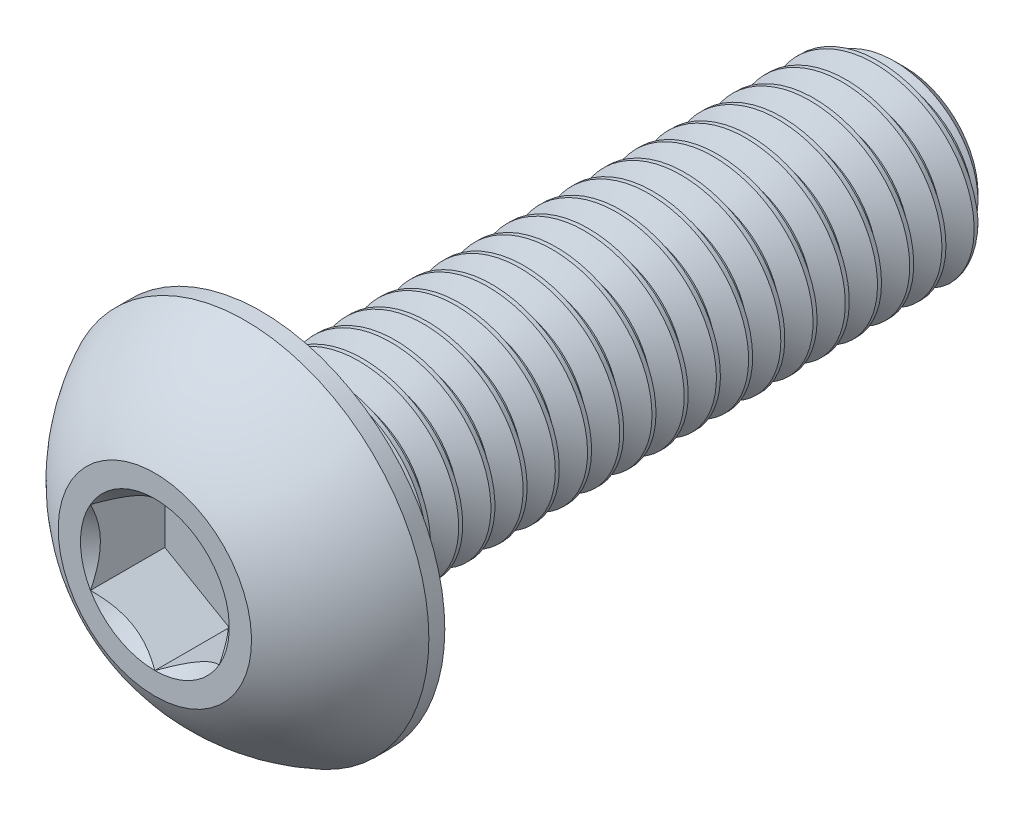
SolidWorks part; units mm, degrees
ref_plane "Front" through (0, 0, 0) normal (0, 0, 1) x (1, 0, 0)
ref_plane "Top" through (0, 0, 0) normal (0, 1, 0) x (1, 0, 0)
ref_plane "Right" through (0, 0, 0) normal (1, 0, 0) x (0, 0, -1)
sketch "Sketch1" plane through (0, 0, 0) normal (1, 0, 0) x (0, 0, -1)
  line L2 (1.65, 1.5) -> (11.65, 1.5)
  line L3 (11.65, 1.5) -> (11.65, 0)
  line L4 (11.65, 0) -> (1.65, 0)
  line L6 (1.4025, 2.85) -> (1.65, 2.85) construction
  line L7 (11.65, 1.5) -> (11.65, -1.5) construction
  line L8 (0, 0) -> (1.65, 0) construction
  line L9 (1.65, 2.85) -> (1.65, -2.85) construction
  line L11 (1.65, 1.5) -> (1.65, 0)
  line L13 (0, 1) -> (0, -1) construction
  line L14 (0, 1) -> (0, 1.5) construction
  arc A3 (0, 1.5) -> (1.4025, 2.85) centre (2.7948, 0) cw construction
  dimension "D1" = 0.2475
  dimension "Head Ht" = 1.65
  dimension "Head Dia" = 5.7
  dimension "Dia" = 3
  dimension "Lg" = 10
  dimension "Hex" = 2
revolve "Revolve1" add sketch "Sketch1" angle 360 mid plane about L4
sketch "Sketch3" plane through (0, 0, -11.65) normal (0, 0, -1) x (-1, 0, 0)
  circle A0 centre (0, 0) radius 1.5
curve "Helix/Spiral1" pitch 0.5 height 10.5 radius 1.5 centre (0, 0, -11.65) axis (0, 0, 1) start towards (0, 1, 0)
sketch "Sketch2" plane through (0, 0, 0) normal (1, 0, 0) x (0, 0, -1)
  line L0 (11.65, 1.5) -> (12.0875, 1.5)
  line L1 (12.0875, 1.5) -> (11.9, 1.1752)
  line L2 (11.9, 1.1752) -> (11.8375, 1.1752)
  line L3 (11.8375, 1.1752) -> (11.65, 1.5)
  line L4 (11.7438, 1.3376) -> (11.9938, 1.3376) construction
  dimension "D1" = 60
  dimension "D2" = 0.0625
  dimension "D3" = 0.25
chamfer "Chamfer1" distance 0.375 angle 45 1 edges at (0, 1.5, -11.65)
sweep "Cut-Sweep1" cut profiles "Sketch2" path "Helix/Spiral1" align with end faces yes
sketch "Sketch7" plane through (0, 0, 0) normal (1, 0, 0) x (0, 0, -1)
  line L6 (1.4025, 2.85) -> (1.65, 2.85) construction
  line L8 (0, 0) -> (1.65, 0) construction
  line L11 (1.65, 2.85) -> (1.65, -2.85) construction
  line L12 (1.4025, 2.85) -> (1.65, 2.85)
  line L13 (0, 0) -> (1.65, 0)
  line L14 (0, 1) -> (0, -1) construction
  line L15 (1.65, 2.85) -> (1.65, 0)
  line L16 (0, 1.5) -> (0, 0)
  arc A2 (1.4025, 2.85) -> (0, 1.5) centre (2.7948, 0) ccw construction
  arc A3 (1.4025, 2.85) -> (0, 1.5) centre (2.7948, 0) ccw
revolve "Revolve2" add sketch "Sketch7" angle 360 mid plane about L13
sketch "Sketch5" plane through (0, 0, 0) normal (0, 0, 1) x (1, 0, 0)
  line L1 (1, -0.5774) -> (1, 0.5774)
  line L2 (1, 0.5774) -> (0, 1.1547)
  line L3 (0, 1.1547) -> (-1, 0.5774)
  line L4 (-1, 0.5774) -> (-1, -0.5774)
  line L5 (-1, -0.5774) -> (0, -1.1547)
  line L6 (0, -1.1547) -> (1, -0.5774)
  circle A0 centre (0, 0) radius 1 construction
extrude "Cut-Extrude2" cut sketch "Sketch5" against normal blind 1.155
sketch "Sketch6" plane through (0, 0, 0) normal (0, 0, 1) x (1, 0, 0)
  circle A0 centre (0, 0) radius 1.1547
extrude "Cut-Extrude3" cut sketch "Sketch6" against normal blind 1.155 draft 45
sketch "Sketch9" [suppressed] plane through (0, 0, -4.2164) normal (0, 0, 1) x (1, 0, 0)
  circle A2 centre (0, 0) radius 3.9687
extrude "Boss-Extrude2" [suppressed] add sketch "Sketch9" against normal offset from surface (9.525 mm away) 28.575 up to face at (0, 1.125, -11.65)
sketch "Sketch10" plane through (0, 0, 0) normal (1, 0, 0) x (0, 0, -1)
  line L0 (11.65, 1.5) -> (11.65, -1.5) construction
  point P0 (10.9, -1.5)
  dimension "D1" = 0.75
equation "\"D3@Helix/Spiral1\" = \"Lg@Sketch1\" + \"D4@Helix/Spiral1\""
equation "\"D2@Sketch2\" = \"D4@Helix/Spiral1\" * .125"
equation "\"D3@Sketch2\" = \"D4@Helix/Spiral1\" * .5"
equation "\"D1@Chamfer1\" = \"D4@Helix/Spiral1\" * .75"
equation "\"D1@Cut-Extrude2\" = \"Head Ht@Sketch1\" * .7"
equation "\"D1@Sketch1\" = \"Head Ht@Sketch1\" * .15"
equation "\"D1@Sketch10\" = \"D4@Helix/Spiral1\" * 1.5"
equation "\"D1@Cut-Extrude3\" = \"D1@Cut-Extrude2\""
